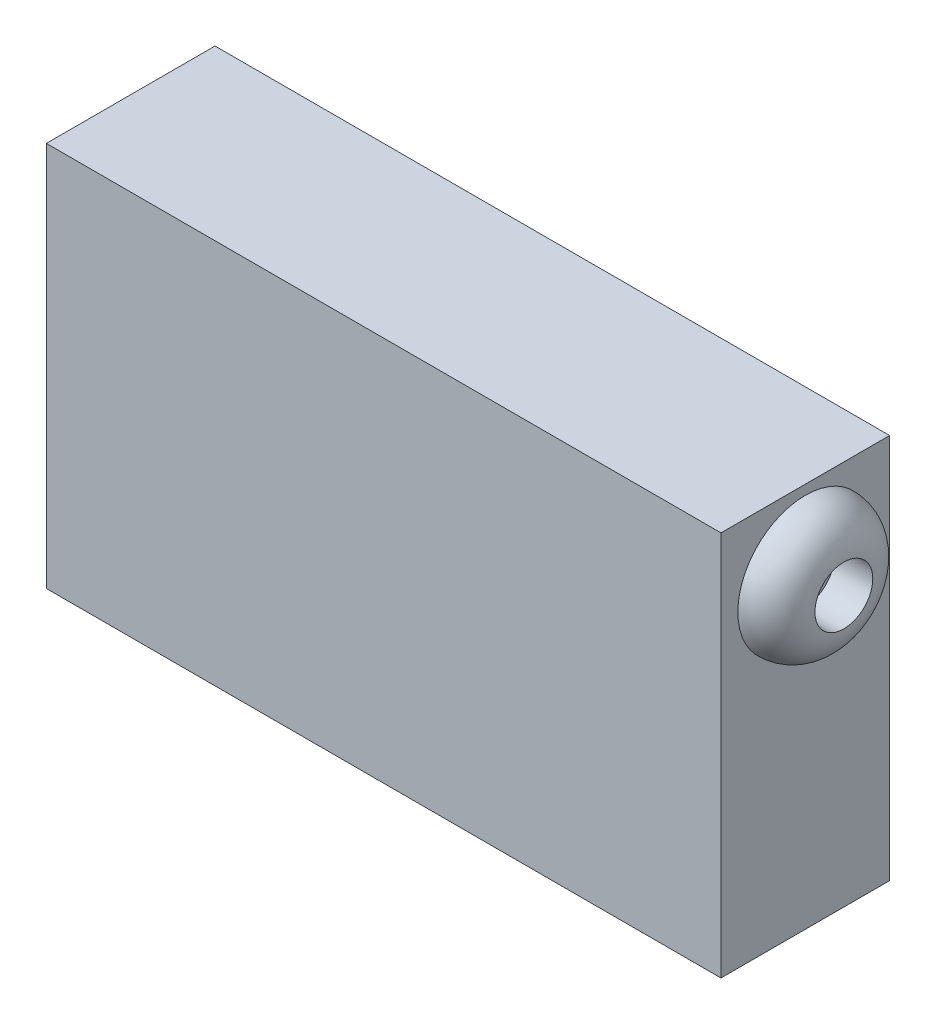
SolidWorks part; units mm, degrees
ref_plane "Front Plane" through (0, 0, 0) normal (0, 0, 1) x (1, 0, 0)
ref_plane "Top Plane" through (0, 0, 0) normal (0, 1, 0) x (1, 0, 0)
ref_plane "Right Plane" through (0, 0, 0) normal (1, 0, 0) x (0, 0, -1)
sketch "Sketch1" plane through (0, 0, 0) normal (0, 1, 0) x (1, 0, 0)
  line L1 (-17.5, 4.375) -> (17.5, 4.375)
  line L2 (-17.5, 4.375) -> (-17.5, -4.375)
  line L3 (-17.5, -4.375) -> (17.5, -4.375)
  line L4 (17.5, 4.375) -> (17.5, -4.375)
  point P0 (0, 0)
  dimension "D1" = 35
  dimension "D2" = 8.75
extrude "Boss-Extrude1" add sketch "Sketch1" along normal blind 20
sketch "Sketch2" plane through (17.5, 0, 0) normal (1, 0, 0) x (0, 0, -1)
  circle A0 centre (0, 16) radius 3.5
  dimension "D1" = 16
extrude "Boss-Extrude2" add sketch "Sketch2" along normal blind 2
sketch "Sketch3" plane through (19.5, 0, 0) normal (1, 0, 0) x (0, 0, -1)
  circle A0 centre (0, 16) radius 1.5
extrude "Cut-Extrude1" cut sketch "Sketch3" against normal blind 2
fillet "Fillet1" radius 2 1 edges at (19.5, 16, -3.5)
